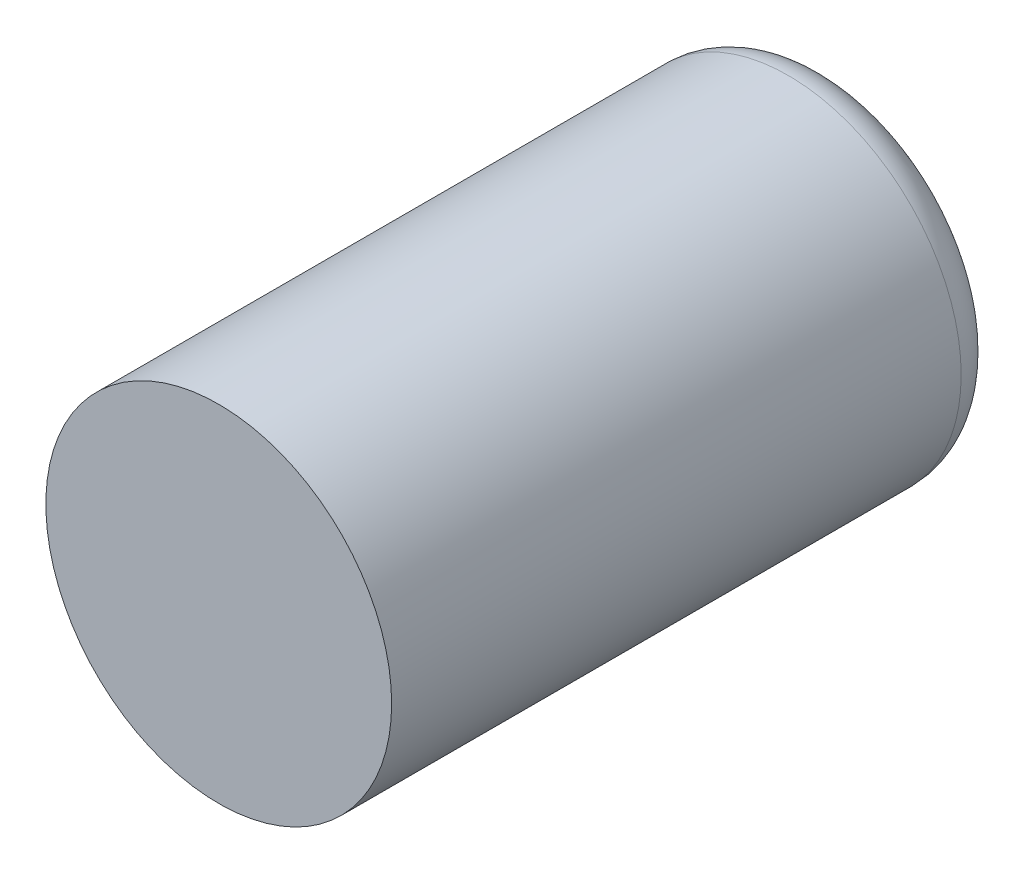
SolidWorks part; units mm, degrees
ref_plane "Front Plane" through (0, 0, 0) normal (0, 0, 1) x (1, 0, 0)
ref_plane "Top Plane" through (0, 0, 0) normal (0, 1, 0) x (1, 0, 0)
ref_plane "Right Plane" through (0, 0, 0) normal (1, 0, 0) x (0, 0, -1)
sketch "Sketch1" plane through (0, 0, 0) normal (0, 1, 0) x (1, 0, 0)
  line L0 (6.5, 0) -> (0, 0)
  line L1 (0, 0) -> (0, -30)
  line L2 (0, -30) -> (8.5, -30)
  line L3 (8.5, -30) -> (8.5, -2)
  line L4 (0, 0.0013) -> (0, -30) construction
  arc A0 (8.5, -2) -> (6.5, 0) centre (6.5, -2) ccw
revolve "Revolve1" add sketch "Sketch1" angle 360 about L4 reverse direction yes
